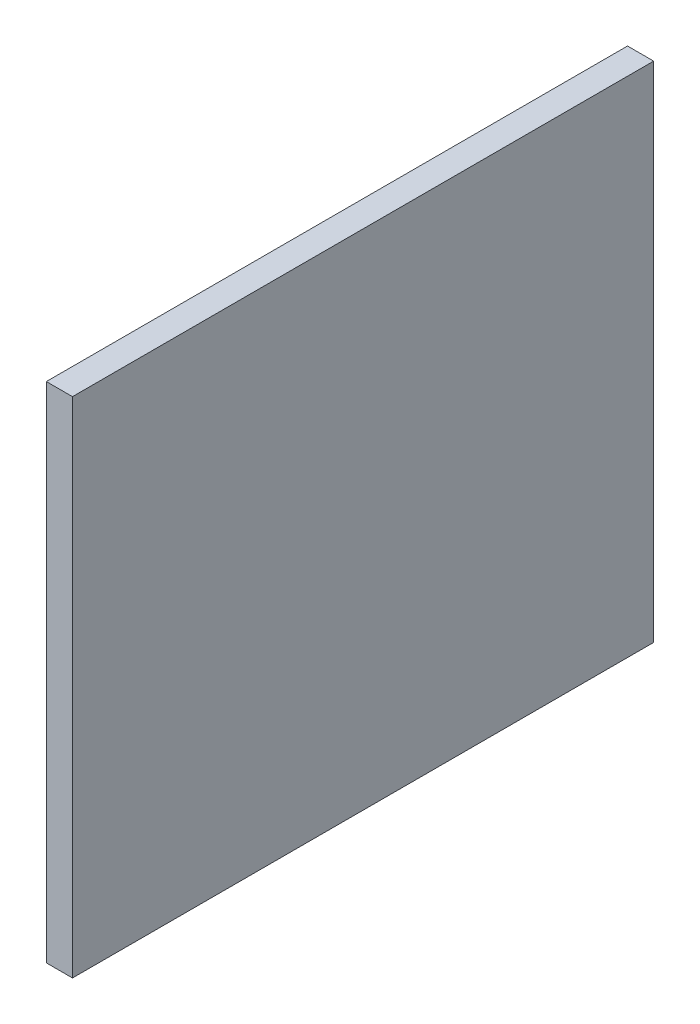
SolidWorks part; units mm, degrees
ref_plane "Front" through (0, 0, 0) normal (0, 0, 1) x (1, 0, 0)
ref_plane "Top" through (0, 0, 0) normal (0, 1, 0) x (1, 0, 0)
ref_plane "Right" through (0, 0, 0) normal (1, 0, 0) x (0, 0, -1)
sketch "Sketch1" plane through (0, 0, 0) normal (1, 0, 0) x (0, 0, -1)
  line L1 (-200, -173.25) -> (200, -173.25)
  line L2 (-200, -173.25) -> (-200, 173.25)
  line L3 (-200, 173.25) -> (200, 173.25)
  line L4 (200, -173.25) -> (200, 173.25)
  line L5 (-200, -173.25) -> (200, 173.25) construction
  line L6 (-200, 173.25) -> (200, -173.25) construction
  point P0 (0, 0)
  dimension "D1" = 400
  dimension "D2" = 346.5
extrude "Boss-Extrude1" add sketch "Sketch1" along normal blind 18
